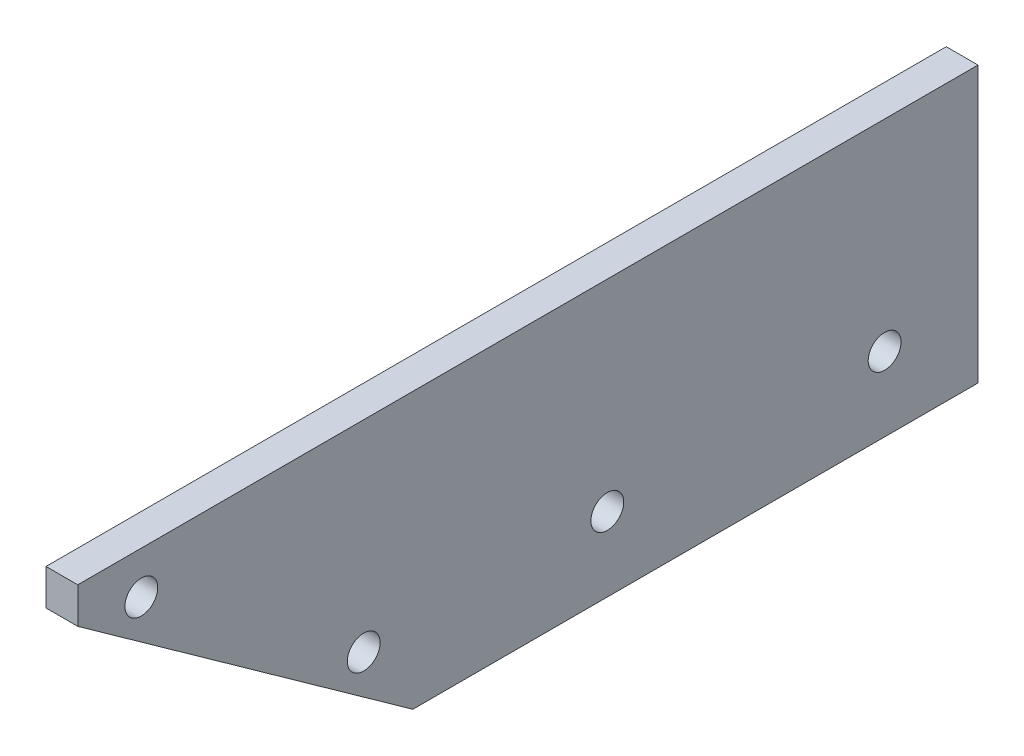
SolidWorks part; units mm, degrees
ref_plane "Ebene vorne" through (0, 0, 0) normal (0, 0, 1) x (1, 0, 0)
ref_plane "Ebene oben" through (0, 0, 0) normal (0, 1, 0) x (1, 0, 0)
ref_plane "Ebene rechts" through (0, 0, 0) normal (1, 0, 0) x (0, 0, -1)
sketch "Skizze1" plane through (0, 0, 0) normal (1, 0, 0) x (0, 0, -1)
  line L1 (0, 0) -> (85, 0)
  line L2 (0, 0) -> (0, 26)
  line L3 (0, 26) -> (85, 26)
  line L4 (85, 0) -> (85, 26)
  dimension "D1" = 85
  dimension "D2" = 26
extrude "Aufsatz-Linear austragen1" add sketch "Skizze1" along normal blind 3
sketch "Skizze2" plane through (3, 0, 0) normal (1, 0, 0) x (0, 0, -1)
  line L0 (6, 0) -> (6, 22) construction
  line L1 (0, 0) -> (85, 0) construction
  line L2 (27, 0) -> (27, 7) construction
  line L3 (50, 0) -> (50, 7) construction
  line L4 (76.1837, 0) -> (76.1837, 7) construction
  line L5 (76.1837, 7) -> (50, 7) construction
  line L6 (50, 7) -> (27, 7) construction
  line L7 (0, 26) -> (0, 0) construction
  circle A0 centre (6, 22) radius 1.55
  circle A1 centre (27, 7) radius 1.55
  circle A2 centre (50, 7) radius 1.55
  circle A3 centre (76.1837, 7) radius 1.55
  point P16 (0, 0)
  point P17 (74.0084, 7)
  point P18 (76.1837, 7)
  dimension "D6" = 3.1
  dimension "D1" = 21
  dimension "D2" = 23
  dimension "D3" = 15
  dimension "D4" = 7
  dimension "D5" = 6
extrude "Schnitt-Linear austragen1" cut sketch "Skizze2" against normal through all
sketch "Skizze3" plane through (3, 0, 0) normal (1, 0, 0) x (0, 0, -1)
  line L0 (0, 22.599) -> (31.6386, 0)
  line L1 (0, 26) -> (0, 0) construction
  line L2 (0, 0) -> (85, 0) construction
  line L3 (31.6386, 0) -> (0, 0)
  line L4 (0, 0) -> (0, 22.599)
  line L5 (6, 22) -> (27, 7) construction
  dimension "D1" = 3
extrude "Schnitt-Linear austragen2" cut sketch "Skizze3" against normal through all
